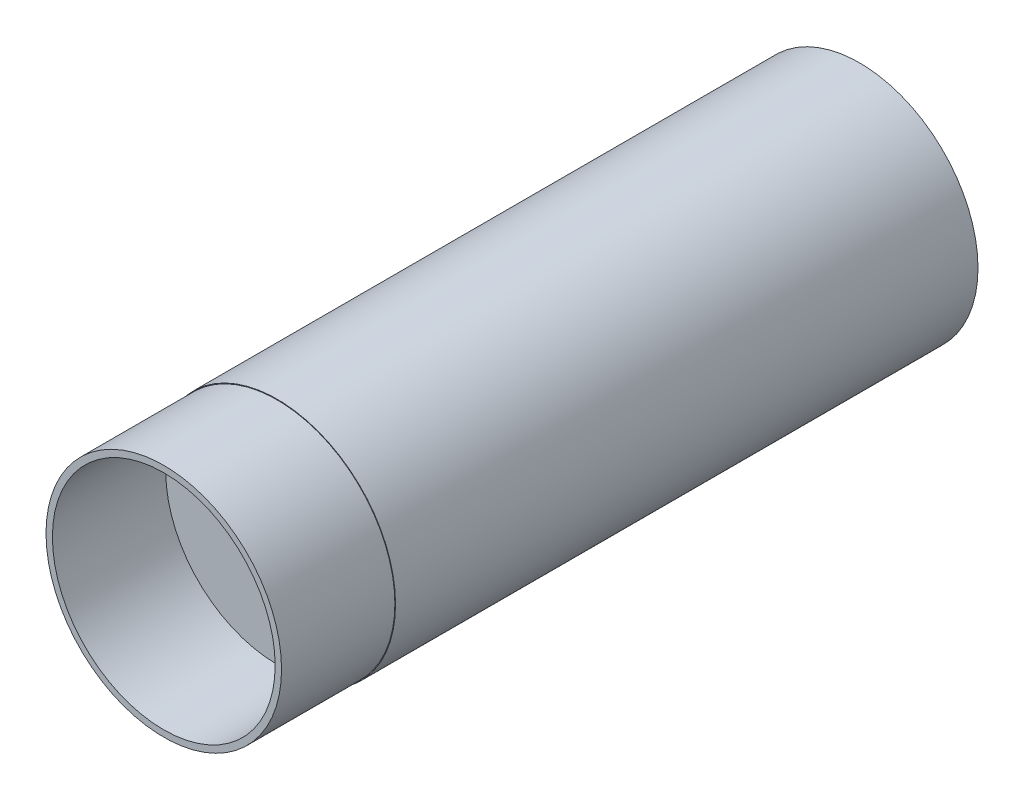
SolidWorks part; units mm, degrees
note: The reader was unsure of these and kept them because the rebuilt part matched: shared geometry of "Sketch1<2>".
ref_plane "Front Plane" through (0, 0, 0) normal (0, 0, 1) x (1, 0, 0)
ref_plane "Top Plane" through (0, 0, 0) normal (0, 1, 0) x (1, 0, 0)
ref_plane "Right Plane" through (0, 0, 0) normal (1, 0, 0) x (0, 0, -1)
sketch "Sketch1" plane through (0, 0, 0) normal (0, 0, 1) x (1, 0, 0)
  circle A0 centre (0, 0) radius 18.5
  circle A1 centre (0, 0) radius 17.4
  circle A2 centre (0, 0) radius 18.4
  dimension "D1" = 37
  dimension "D2" = 1.1
  dimension "D3" = 0.1
extrude "Boss-Extrude1" add sketch "Sketch1" along normal blind 17.71 contours A2 A1
extrude "Boss-Extrude2" add sketch "Sketch1<2>" against normal blind 91 contours A0 A1 | A1 | A0 A2
sketch "Sketch1<2>" plane through (0, 0, 0) normal (0, 0, 1) x (1, 0, 0) same geometry as "Sketch1"
